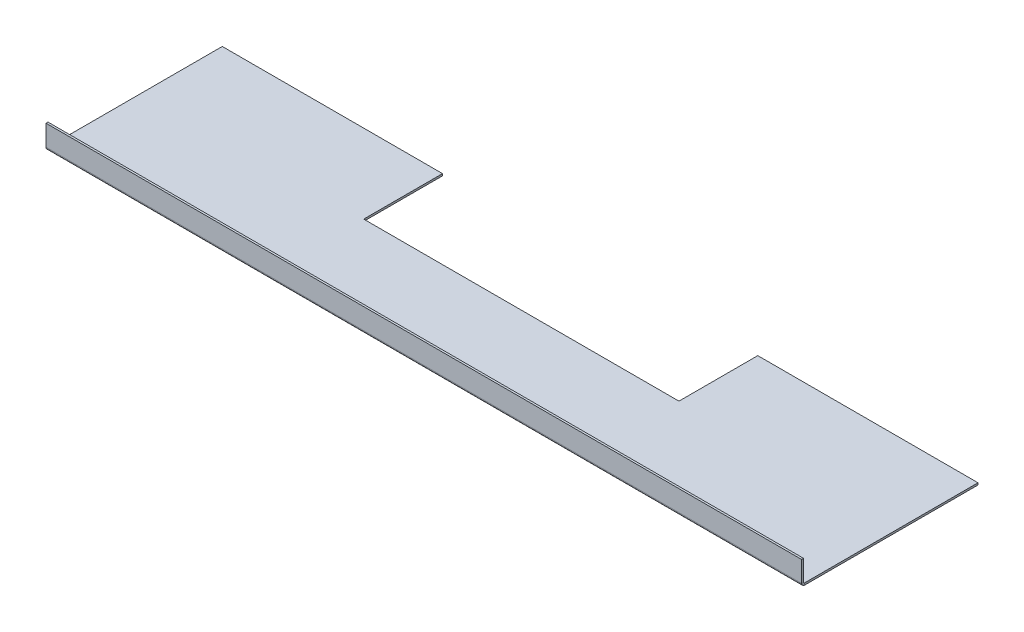
SolidWorks part; units mm, degrees
note: The reader was unsure of these and kept them because the rebuilt part matched: flange length of "Edge-Flange1".
ref_plane "Front Plane" through (0, 0, 0) normal (0, 0, 1) x (1, 0, 0)
ref_plane "Top Plane" through (0, 0, 0) normal (0, 1, 0) x (1, 0, 0)
ref_plane "Right Plane" through (0, 0, 0) normal (1, 0, 0) x (0, 0, -1)
sketch "Sketch1" plane through (0, 0, 0) normal (0, 1, 0) x (1, 0, 0)
  line L0 (0, -69.85) -> (0, 3.4735) construction
  line L1 (-304.419, 69.85) -> (-127, 69.85)
  line L2 (-304.419, 69.85) -> (-304.419, -69.85)
  line L3 (-304.419, -69.85) -> (304.419, -69.85)
  line L4 (304.419, 69.85) -> (304.419, -69.85)
  line L5 (-304.419, 69.85) -> (304.419, -69.85) construction
  line L6 (-304.419, -69.85) -> (304.419, 69.85) construction
  line L8 (-127, 69.85) -> (-127, 6.35)
  line L9 (-127, 6.35) -> (127, 6.35)
  line L10 (127, 69.85) -> (127, 6.35)
  line L11 (127, 69.85) -> (304.419, 69.85)
  point P0 (0, 0)
  dimension "D1" = 139.7
  dimension "D2" = 608.838
  dimension "D3" = 254
  dimension "D4" = 127
  dimension "D5" = 63.5
base flange "Base-Flange1" sketch "Sketch1" thickness 1.5875 reverse thickness direction no parameters "D1"=0.7366
edge flange "Edge-Flange1" sketch "Sketch15" flange angle 90 flange length 19.05 flange position bend outside bend radius 0.7366 thickness 1.5875 relief rectangular parameters "D6"=10
sketch "Sketch15" plane through (0, 0, 69.85) normal (0, 0, 1) x (1, 0, 0)
  line L0 (-304.419, 0) -> (304.419, 0) construction
  line L1 (-304.419, 0) -> (304.419, 0)
  line L2 (-304.419, 0) -> (-304.419, 17.4625)
  line L3 (-304.419, 17.4625) -> (304.419, 17.4625)
  line L4 (304.419, 17.4625) -> (304.419, 0)
bend "EdgeBend1" bend radius 0.7366 bend angle 90 parameters "D5"=1
sketch "Bend-Lines1" [suppressed] plane through (0, 0, 0) normal (0, 1, 0) x (1, 0, 0)
sketch "Bounding-Box1" [suppressed] plane through (0, 0, 0) normal (0, 1, 0) x (1, 0, 0)
sheet metal parameters "Sheet-Metal1" thickness 1.5875 parameters "D1"=0.7366
flat pattern "Flat-Pattern1" [suppressed]
sketch "Bend-Lines2" plane through (0, 0, 0) normal (0, 1, 0) x (1, 0, 0)
sketch3d "Bounding-Box2" [suppressed]
  line L0 (-291.6936, -71.12, 0) -> (291.6936, -71.12, 0) construction
  line L1 (-291.6936, 71.12, 0) -> (291.6936, 71.12, 0) construction
  line L2 (-291.6936, -71.12, 0) -> (-291.6936, 71.12, 0) construction
  line L3 (291.6936, -71.12, 0) -> (291.6936, 71.12, 0) construction
sheet metal parameters "Sheet-Metal2" thickness 1.5875 parameters "D1"=0.7366
flat pattern "Flat-Pattern1"
sketch "Bend-Lines2" plane through (0, 0, 0) normal (0, 1, 0) x (1, 0, 0)
  line L0 (-304.419, -71.0519) -> (304.419, -71.0519) construction
  line L1 (-304.419, -71.0519) -> (304.419, -71.0519) construction
sketch3d "Bounding-Box2" [suppressed]
  line L0 (304.419, -88.9798, 0) -> (-304.419, -88.9798, 0) construction
  line L1 (304.419, 69.85, 0) -> (-304.419, 69.85, 0) construction
  line L2 (304.419, -88.9798, 0) -> (304.419, 69.85, 0) construction
  line L3 (-304.419, -88.9798, 0) -> (-304.419, 69.85, 0) construction
bend of the flat pattern "Flatten-<EdgeBend1>1"
